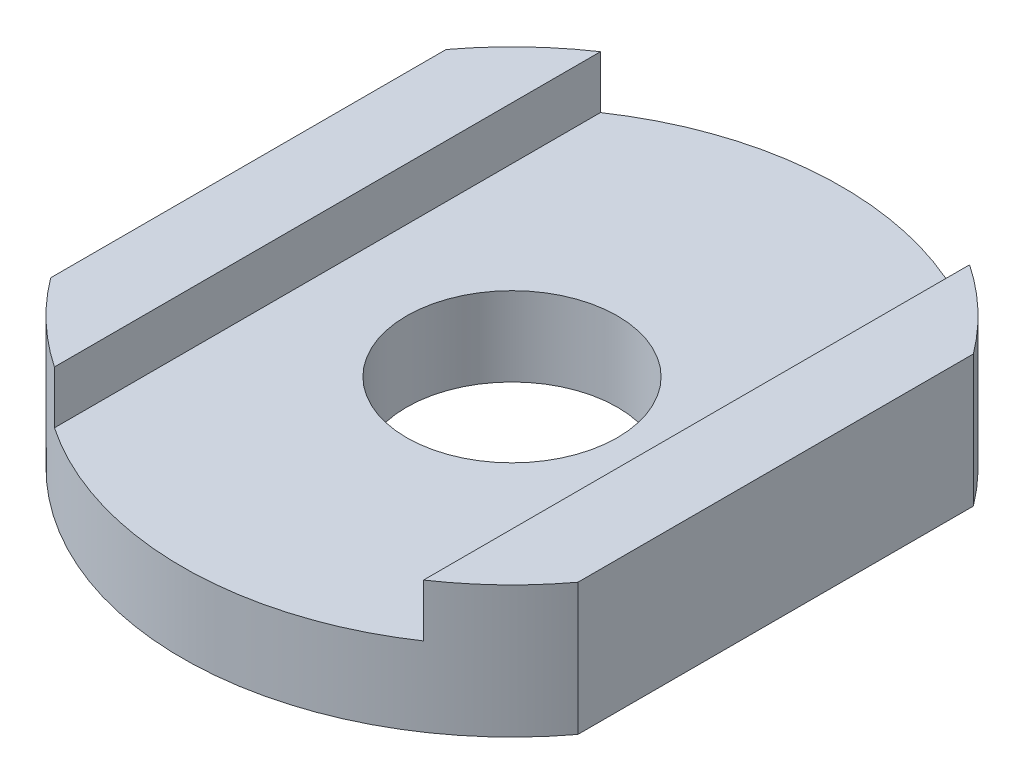
SolidWorks part; units mm, degrees
ref_plane "Front Plane" through (0, 0, 0) normal (0, 0, 1) x (1, 0, 0)
ref_plane "Top Plane" through (0, 0, 0) normal (0, 1, 0) x (1, 0, 0)
ref_plane "Right Plane" through (0, 0, 0) normal (1, 0, 0) x (0, 0, -1)
sketch "Sketch1" plane through (0, 0, 0) normal (0, 1, 0) x (1, 0, 0)
  line L0 (7, 10.3562) -> (7, -10.3562)
  line L1 (10, 7.5) -> (10, -7.5)
  line L2 (0, 15.8512) -> (0, -17.5845) construction
  line L3 (-10, 7.5) -> (-10, -7.5)
  line L4 (-7, 10.3562) -> (-7, -10.3562)
  circle A0 centre (0, 0) radius 12.5
  circle A1 centre (0, 0) radius 4
  dimension "D1" = 25
  dimension "D2" = 8
  dimension "D3" = 3
  dimension "D4" = 10
extrude "Boss-Extrude1" add sketch "Sketch1" along normal blind 3 contours A0 L2 A1 L0 | L2 A0 L4 A1 region at (6.7404, 0, 0) region at (-0.2596, 0, -8.25)
extrude "Boss-Extrude2" add sketch "Sketch1<3>" along normal blind 5 contours L0 A0 L1 | L4 A0 L3 region at (8.4223, 0, 0) region at (-8.4223, 0, 0)
sketch "Sketch1<3>" plane through (0, 0, 0) normal (0, 1, 0) x (1, 0, 0) same geometry as "Sketch1"
